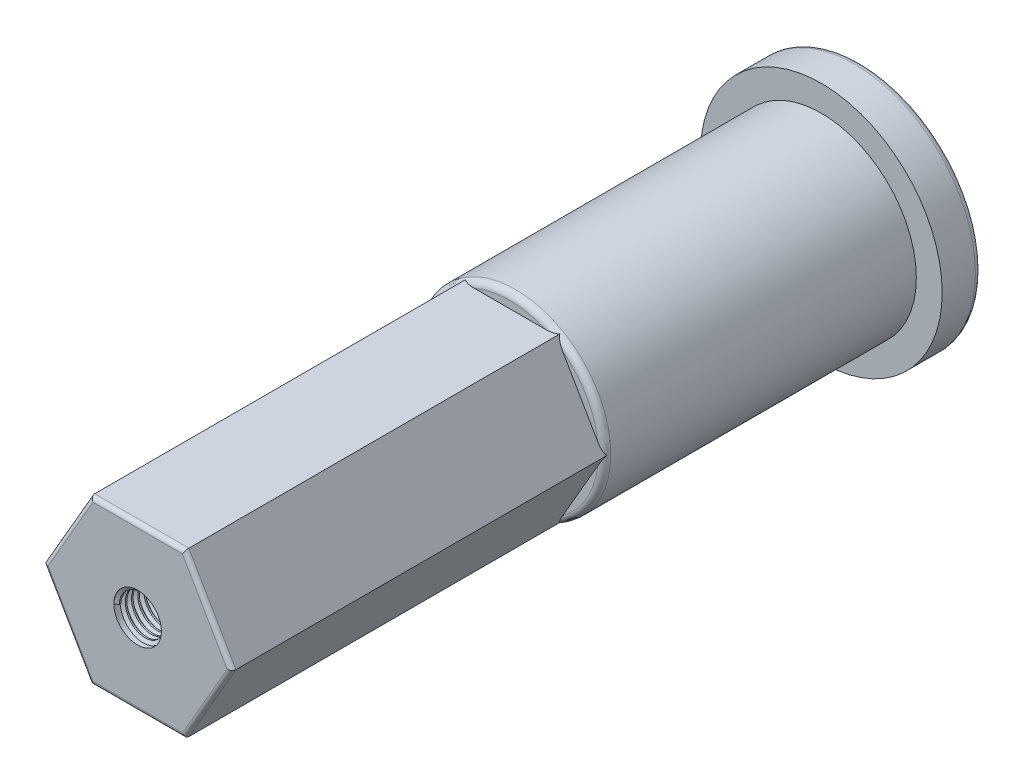
SolidWorks part; units mm, degrees
ref_plane "Alzado" through (0, 0, 0) normal (0, 0, 1) x (1, 0, 0)
ref_plane "Planta" through (0, 0, 0) normal (0, 1, 0) x (1, 0, 0)
ref_plane "Vista lateral" through (0, 0, 0) normal (1, 0, 0) x (0, 0, -1)
sketch "Croquis1" plane through (0, 0, 0) normal (0, 0, 1) x (1, 0, 0)
  circle A0 centre (0, 0) radius 5.85
  dimension "D1" = 11.7
extrude "Saliente-Extruir1" add sketch "Croquis1" along normal blind 35
sketch "Croquis2" plane through (0, 0, 35) normal (0, 0, 1) x (1, 0, 0)
  circle A0 centre (0, 0) radius 4.6
  dimension "D1" = 9.2
extrude "Cortar-Extruir1" cut sketch "Croquis2" against normal blind 33.09 flip side to cut
sketch "Croquis3" plane through (0, 0, 35) normal (0, 0, 1) x (1, 0, 0)
  line L1 (4.5611, 0) -> (2.2805, 3.95)
  line L2 (2.2805, 3.95) -> (-2.2805, 3.95)
  line L3 (-2.2805, 3.95) -> (-4.5611, 0)
  line L4 (-4.5611, 0) -> (-2.2805, -3.95)
  line L5 (-2.2805, -3.95) -> (2.2805, -3.95)
  line L6 (2.2805, -3.95) -> (4.5611, 0)
  circle A0 centre (0, 0) radius 3.95 construction
  dimension "D1" = 3.95
extrude "Cortar-Extruir3" cut sketch "Croquis3" against normal blind 18 flip side to cut
sketch "Croquis4" plane through (0, 0, 0) normal (0, 0, -1) x (-1, 0, 0)
  circle A0 centre (0, 0) radius 2.45
  dimension "D1" = 4.9
extrude "Cortar-Extruir4" cut sketch "Croquis4" against normal blind 1.5
sketch "Croquis5" plane through (0, 0, 35) normal (0, 0, 1) x (1, 0, 0)
  circle A0 centre (0, 0) radius 1.15
  dimension "D1" = 2.3
extrude "Cortar-Extruir5" cut sketch "Croquis5" against normal up to next
sketch "Croquis6" plane through (0, 0, 0) normal (0, 0, -1) x (-1, 0, 0)
  circle A0 centre (0, 0) radius 4
  dimension "D1" = 8
extrude "Cortar-Extruir6" cut sketch "Croquis6" against normal blind 0.1
fillet "Redondeo1" radius 0.2 6 edges at (-3.4208, 1.975, 35) (-3.4208, -1.975, 35) (0, -3.95, 35) (3.4208, -1.975, 35) (3.4208, 1.975, 35) (0, 3.95, 35)
fillet "Redondeo2" radius 0.3 1 edges at (4.6, 0, 17)
fillet "Redondeo3" radius 0.3 1 edges at (5.85, 0, 0)
sketch "Croquis7" plane through (0, 0, 0) normal (0, 0, -1) x (-1, 0, 0)
  line L0 (2.3094, 0) -> (4, 0) construction
  line L1 (2.3094, 0) -> (1.1547, 2)
  line L2 (1.1547, 2) -> (-1.1547, 2)
  line L3 (-1.1547, 2) -> (-2.3094, 0)
  line L4 (-2.3094, 0) -> (-1.1547, -2)
  line L5 (-1.1547, -2) -> (1.1547, -2)
  line L6 (1.1547, -2) -> (2.3094, 0)
  circle A0 centre (0, 0) radius 2 construction
  circle A1 centre (0, 0) radius 4 construction
  dimension "D1" = 2
extrude "Cortar-Extruir7" cut sketch "Croquis7" against normal blind 30.5
fillet "Redondeo4" radius 0.4 6 edges at (-1.7321, -1, 1.5) (0, -2, 1.5) (1.7321, -1, 1.5) (-1.7321, 1, 1.5) (0, 2, 1.5) (1.7321, 1, 1.5)
thread "Rosca1" pitch 0.3 method extrude profile "Perfil de rosca1" start angle 0, offset 0, length 0, pitch 0.3, diameter 2.3
ref_plane "Plano1" through (-1.15, 0, 35) normal (0, -1, 0) x (-1, 0, 0)
sketch "Perfil de rosca1" plane through (-1.15, 0, 35) normal (0, -1, 0) x (-1, 0, 0)
  line L0 (0, 0) -> (0, 0.3) construction
  line L11 (0, 0) -> (0, 0.2625)
  line L12 (0, 0.2625) -> (-0.1624, 0.1687)
  line L13 (-0.1624, 0.1687) -> (-0.1624, 0.0937)
  line L15 (-0.1624, 0.0937) -> (0, 0)
  line L17 (-0.1624, 0.1312) -> (0, 0.1312) construction
  point P2 (0, 0)
  dimension "Pitch" = 0.3
  dimension "Profile_Angle" = 60
  dimension "Profile_Land" = 0.075
  dimension "Profile_Height" = 0.1624
